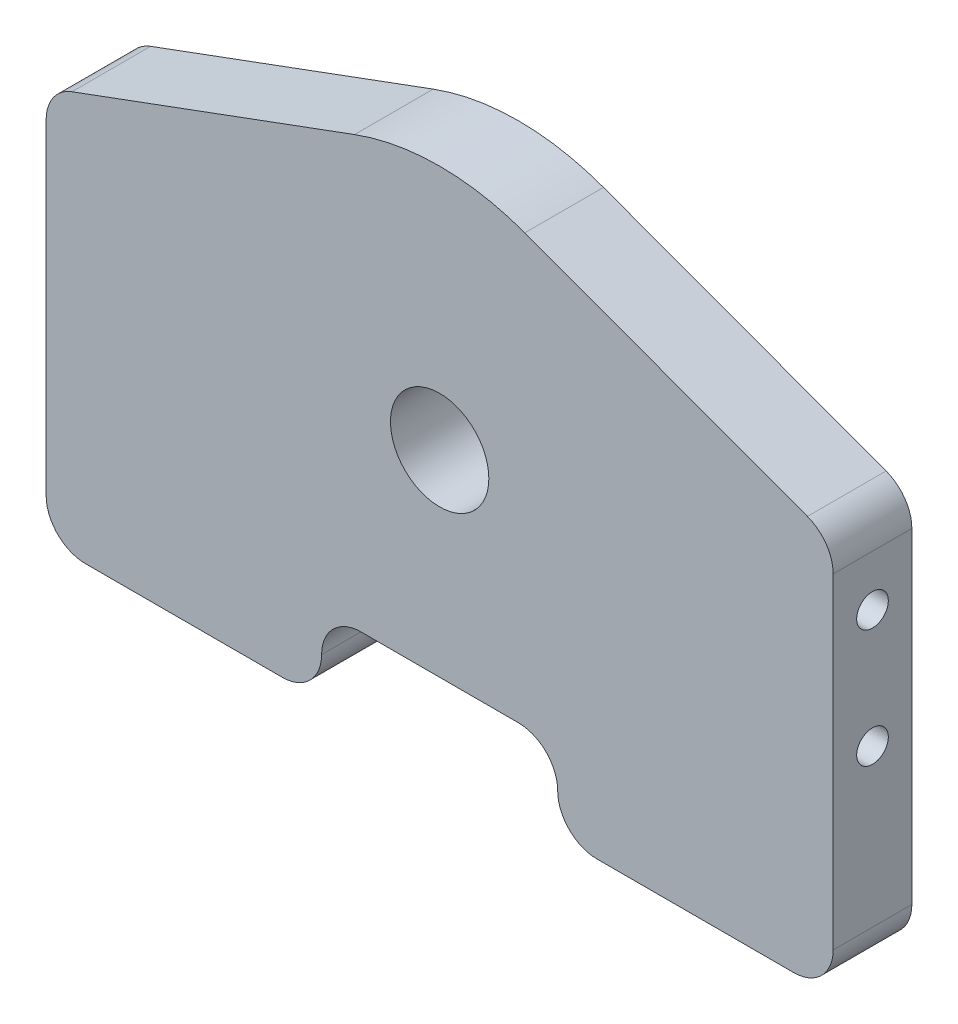
SolidWorks part; units mm, degrees
material "6061-T6 (SS)"
ref_plane "Front Plane" through (0, 0, 0) normal (0, 0, 1) x (1, 0, 0)
ref_plane "Top Plane" through (0, 0, 0) normal (0, 1, 0) x (1, 0, 0)
ref_plane "Right Plane" through (0, 0, 0) normal (1, 0, 0) x (0, 0, -1)
sketch "Sketch1" plane through (0, 0, 0) normal (0, 0, 1) x (1, 0, 0)
  line L1 (-63.5, 0) -> (63.5, 0)
  line L2 (-63.5, 0) -> (-63.5, 152.4)
  line L3 (-63.5, 152.4) -> (63.5, 152.4)
  line L4 (63.5, 0) -> (63.5, 152.4)
  dimension "D1" = 127
  dimension "D2" = 152.4
extrude "Boss-Extrude1" add sketch "Sketch1" along normal blind 12.7
sketch "Sketch2" plane through (0, 0, 12.7) normal (0, 0, 1) x (1, 0, 0)
  line L0 (-63.5, 63.327) -> (-13.7357, 81.6848)
  line L1 (-63.5, 152.4) -> (-63.5, 0) construction
  line L3 (63.5, 63.327) -> (13.7357, 81.6848)
  line L4 (63.5, 0) -> (63.5, 152.4) construction
  line L6 (-63.5, 63.327) -> (-63.5, 152.4)
  line L7 (-63.5, 152.4) -> (63.5, 152.4)
  line L8 (63.5, 152.4) -> (63.5, 63.327)
  circle A0 centre (0, 44.45) radius 7.9375
  circle A1 centre (0, 44.45) radius 39.6875
  line M1 (-63.5, 152.4) -> (-63.5, 0)
  line M3 (63.5, 0) -> (63.5, 152.4)
  line M4 (63.5, 152.4) -> (-63.5, 152.4)
  dimension "D1" = 79.375
extrude "Cut-Extrude1" cut sketch "Sketch2" against normal through all contours A1 L3 L0 M3 M4 M1 | A0 region at (0, 113.353, 12.7) region at (0, 44.45, 12.7)
hole_wizard "1/4-20 Tapped Hole1" positions "Sketch4" profile "Sketch3" tap size "1/4-20" standard "ANSI Inch"
sketch "Sketch4" plane through (63.5, 0, 0) normal (1, 0, 0) x (0, 0, -1)
  line L0 (-6.35, 63.327) -> (-6.35, 50.7135) construction
  line L1 (0, 63.327) -> (-12.7, 63.327) construction
  line L2 (-6.35, 50.7135) -> (-6.35, 31.6635) construction
  line L3 (-6.35, 31.6635) -> (0, 31.6635) construction
  line L4 (0, 0) -> (0, 63.327) construction
  point P2 (-6.35, 50.7135)
  point P6 (-6.35, 31.6635)
  dimension "D1" = 19.05
sketch "Sketch3" plane through (63.5, 50.7135, 6.35) normal (0, 1, 0) x (0, 0, -1)
  line L0 (0, 0) -> (0, 18.0438)
  line L1 (0, 18.0438) -> (2.5527, 16.51)
  line L2 (2.5527, 16.51) -> (2.5527, 0)
  line L5 (2.5527, 0) -> (0, 0)
  line L10 (0, 18.0438) -> (-2.5527, 16.51) construction
  line L11 (0, -6.35) -> (0, 107.95) construction
  dimension "Tap Drill Dia." = 5.1054
  dimension "Tap Drill Depth" = 16.51
  dimension "Drill Angle" = 118
mirror "Mirror1" about plane through (0, 0, 0) normal (1, 0, 0) of "1/4-20 Tapped Hole1"
sketch "Sketch5" plane through (0, 0, 12.7) normal (0, 0, 1) x (1, 0, 0)
  line L0 (-63.5, 0) -> (63.5, 0) construction
  line L1 (-19.05, 0) -> (19.05, 0)
  line L2 (-19.05, 0) -> (-19.05, 12.7)
  line L3 (-19.05, 12.7) -> (19.05, 12.7)
  line L4 (19.05, 0) -> (19.05, 12.7)
  line L5 (63.5, 0) -> (63.5, 63.327) construction
  line L6 (-63.5, 63.327) -> (-63.5, 0) construction
  dimension "D1" = 12.7
  dimension "D2" = 44.45
  dimension "D3" = 44.45
extrude "Cut-Extrude2" cut sketch "Sketch5" against normal through all
fillet "Fillet1" radius 6.35 8 edges at (-19.05, 12.7, 6.35) (19.05, 12.7, 6.35) (19.05, 0, 6.35) (63.5, 0, 6.35) (63.5, 63.327, 6.35) (-63.5, 0, 6.35) (-19.05, 0, 6.35) (-63.5, 63.327, 6.35)
